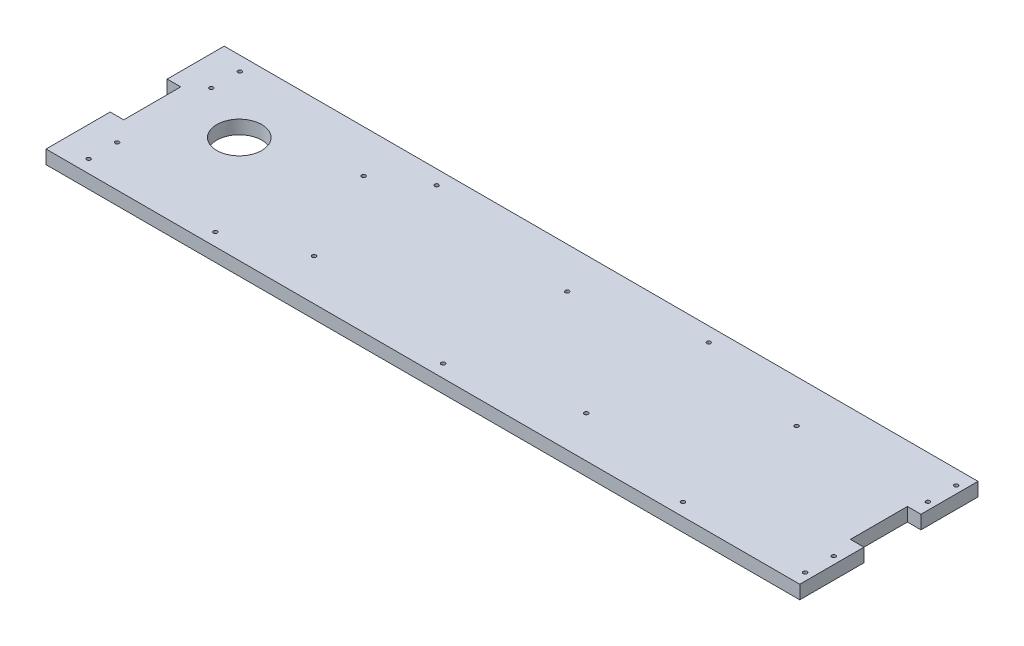
SolidWorks part; units mm, degrees
ref_plane "Front Plane" through (0, 0, 0) normal (0, 0, 1) x (1, 0, 0)
ref_plane "Top Plane" through (0, 0, 0) normal (0, 1, 0) x (1, 0, 0)
ref_plane "Right Plane" through (0, 0, 0) normal (1, 0, 0) x (0, 0, -1)
sketch "Sketch1" plane through (0, 0, 0) normal (0, 0, 1) x (1, 0, 0)
  line L1 (-840.4586, 543.2436) -> (-1897.8999, 543.2436)
  line L2 (-840.4586, 543.2436) -> (-840.4586, 562.2436)
  line L3 (-840.4586, 562.2436) -> (-1897.8999, 562.2436)
  line L4 (-1897.8999, 543.2436) -> (-1897.8999, 562.2436)
  line L6 (-840.4586, 503.2436) -> (-840.4586, 802.9784) construction
  dimension "D2" = 19
extrude "Boss-Extrude1" add sketch "Sketch1" along normal blind 250
sketch "Sketch2" plane through (0, 543.2436, 0) normal (0, -1, 0) x (1, 0, 0)
  circle A3 centre (-1776.3415, 100.4558) radius 31.573
extrude "Cut-Extrude1" cut sketch "Sketch2" against normal blind 19
sketch "Sketch3" plane through (-840.4586, 0, 0) normal (1, 0, 0) x (0, 0, -1)
  line L0 (-250, 543.2436) -> (0, 543.2436) construction
  line L1 (-160, 543.2436) -> (-80, 543.2436)
  line L2 (-160, 543.2436) -> (-160, 562.2436)
  line L3 (-160, 562.2436) -> (-80, 562.2436)
  line L4 (-80, 543.2436) -> (-80, 562.2436)
  line L5 (-250, 562.2436) -> (0, 562.2436) construction
  line L6 (0, 543.2436) -> (0, 562.2436) construction
  dimension "D1" = 80
extrude "Cut-Extrude2" cut sketch "Sketch3" against normal blind 19
sketch "Sketch4" plane through (-1897.8999, 0, 0) normal (-1, 0, 0) x (0, 0, 1)
  line L0 (250, 562.2436) -> (0, 562.2436) construction
  line L1 (160, 562.2436) -> (80, 562.2436)
  line L2 (160, 562.2436) -> (160, 543.2436)
  line L3 (160, 543.2436) -> (80, 543.2436)
  line L4 (80, 562.2436) -> (80, 543.2436)
  line L5 (250, 543.2436) -> (0, 543.2436) construction
extrude "Cut-Extrude3" cut sketch "Sketch4" against normal blind 19
sketch "Sketch5" plane through (0, 562.2436, 0) normal (0, 1, 0) x (1, 0, 0)
  line L0 (-840.4586, -24.1) -> (-840.4586, -16.5) construction
  line L1 (-840.4586, -250) -> (-840.4586, 0) construction
  line L2 (2.0801, -24.1) -> (-1897.9199, -24.1) construction
  line L3 (2.0801, -16.5) -> (-1897.9199, -16.5) construction
  line L4 (-850.7806, -24.1) -> (-850.7806, -16.5) construction
  line L5 (2.0801, -16.5) -> (-1897.9199, -16.5) construction
  line L6 (-850.7806, -20.3) -> (-1897.9199, -20) construction
  line L7 (-850.7806, -55.9) -> (-850.7806, -64.1) construction
  line L8 (-1897.9199, -24.1) -> (-1897.9199, -15.9) construction
  line L9 (2.0801, -55.9) -> (-1897.9199, -55.9) construction
  line L10 (2.0801, -64.1) -> (-1897.9199, -64.1) construction
  line L11 (-850.7806, -60) -> (-1865.9199, -60) construction
  line L16 (-850.7806, -187.9) -> (-850.7806, -196.1) construction
  line L17 (-850.7806, -196.1) -> (-850.7806, -192) construction
  line L18 (-850.7806, -192) -> (-1865.4737, -192) construction
  line L19 (-850.9051, -236.1) -> (-850.9051, -227.9) construction
  line L20 (-850.9051, -227.9) -> (-850.9051, -232) construction
  line L21 (-850.9051, -232) -> (-1866.591, -232) construction
  line L22 (2.0801, -196.1) -> (-1897.9199, -196.1) construction
  line L23 (2.0801, -187.9) -> (-1897.9199, -187.9) construction
  line L24 (2.0801, -227.9) -> (-1897.9199, -227.9) construction
  line L25 (2.0801, -236.1) -> (-1897.9199, -236.1) construction
  point P16 (-1579.8694, -20.0911)
  point P17 (-850.7806, -20.3)
  point P18 (-1197.9965, -20.2005)
  point P21 (-1897.9199, -20)
  point P23 (-1856.033, -20.012)
  point P31 (-1034.9982, -60)
  point P32 (-1359.1998, -57.55)
  point P33 (-1642.3152, -60)
  point P34 (-1856.0979, -60)
  point P41 (-1197.9948, -192)
  point P46 (-1579.8678, -192)
  point P49 (-1856.0313, -192)
  point P52 (-1856.0313, -232)
  point P55 (-1678.4314, -232)
  point P56 (-850.7806, -192)
  point P57 (-1358.748, -232)
  point P58 (-1022.3175, -232)
hole_wizard "M5 Clearance Hole1" positions "3DSketch1" profile "Sketch6" hole size "M5" standard "ISO"
sketch3d "3DSketch1"
  line L0 (-850.7806, 562.2436, 60) -> (-1865.9199, 562.2436, 60) construction
  point P0 (-1856.0979, 562.2436, 60)
  point P3 (-1856.033, 562.2436, 20.012)
  point P6 (-1856.0313, 562.2436, 192)
  point P9 (-1856.0313, 562.2436, 232)
  point P12 (-1678.4314, 562.2436, 232)
  point P15 (-1579.8678, 562.2436, 192)
  point P18 (-1642.3152, 562.2436, 60)
  point P21 (-1579.8694, 562.2436, 20.0911)
  point P24 (-1359.1998, 562.2436, 57.55)
  point P27 (-1358.748, 562.2436, 232)
  point P30 (-1197.9948, 562.2436, 192)
  point P33 (-1197.9965, 562.2436, 20.2005)
  point P36 (-1034.9982, 562.2436, 60)
  point P39 (-1022.3175, 562.2436, 232)
  point P42 (-850.7806, 562.2436, 192)
  point P45 (-850.9051, 562.2436, 232)
  point P48 (-850.7806, 562.2436, 60)
  point P52 (-850.7806, 562.2436, 20.3)
sketch "Sketch6" plane through (-1856.0979, 562.2436, 60) normal (1, 0, 0) x (0, 0, 1)
  line L0 (0, 0) -> (0, 20.6524)
  line L1 (0, 20.6524) -> (2.75, 19)
  line L2 (2.75, 19) -> (2.75, 0)
  line L5 (2.75, 0) -> (0, 0)
  line L10 (0, 20.6524) -> (-2.75, 19) construction
  line L11 (0, -6.35) -> (0, 107.95) construction
  dimension "Hole Dia." = 5.5
  dimension "Hole Depth" = 19
  dimension "Drill Angle" = 118
